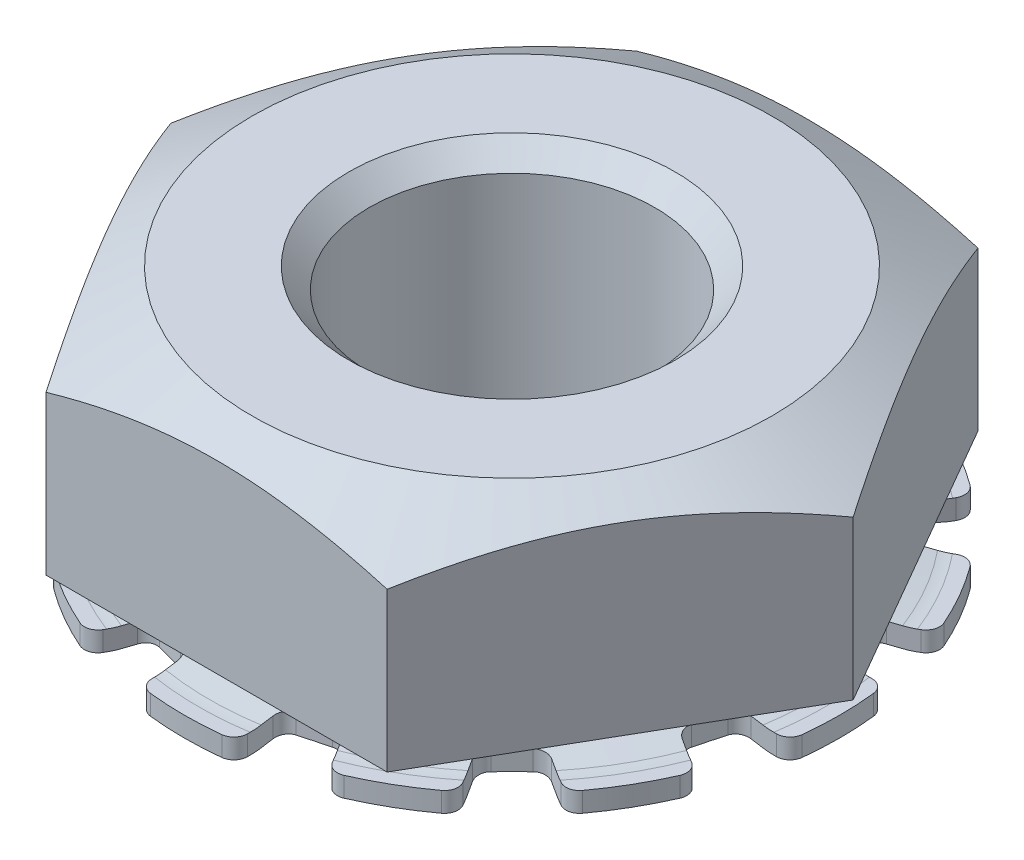
SolidWorks part; units mm, degrees
note: The reader was unsure of these and kept them because the rebuilt part matched: shared geometry of "草图1<3>".
material "铸造碳钢"
ref_plane "前视基准面" through (0, 0, 0) normal (0, 0, 1) x (1, 0, 0)
ref_plane "上视基准面" through (0, 0, 0) normal (0, 1, 0) x (1, 0, 0)
ref_plane "右视基准面" through (0, 0, 0) normal (1, 0, 0) x (0, 0, -1)
sketch "草图1" plane through (0, 0, 0) normal (0, 0, 1) x (1, 0, 0)
  line L0 (0, -97.5064) -> (0, 4777.8117) construction
  line L3 (2.085, 3.28) -> (2.085, 0)
  line L4 (2.085, 0) -> (2.685, 0)
  line L5 (2.685, 0) -> (2.685, 0.29)
  line L6 (2.685, 0.29) -> (2.375, 0.29)
  line L7 (2.375, 0.29) -> (2.375, 0.58)
  line L8 (2.375, 0.58) -> (4.318, 0.58)
  line L9 (4.318, 0.58) -> (4.318, 3.28)
  line L17 (2.375, 0.29) -> (2.085, 0.29) construction
  line L18 (4.5, 0) -> (4.79, 0)
  line L19 (4.5, 0.29) -> (4.79, 0.29)
  line L21 (4.79, 0.29) -> (4.79, 0)
  line L22 (2.685, 0) -> (4.5, 0) construction
  line L23 (2.685, 0.29) -> (4.5, 0)
  line L24 (2.685, 0.58) -> (4.5, 0.29)
  line L25 (2.385, 3.58) -> (3.7984, 3.58)
  line L26 (3.7984, 3.58) -> (4.318, 3.28)
  line L27 (2.385, 3.58) -> (2.085, 3.28)
  dimension "D1" = 45
  dimension "螺纹大径" = 4.17
  dimension "外齿直径" = 9.58
  dimension "螺母厚度" = 3
  dimension "螺母总厚度" = 3.58
  dimension "D4" = 30
  dimension "倒角" = 0.3
  dimension "底部直径" = 5.37
  dimension "六角对边" = 8.636
revolve "旋转1" add sketch "草图1" angle 360 about L0
revolve "旋转2" add sketch "草图1<3>" angle 360 about L0
sketch "草图1<3>" plane through (0, 0, 0) normal (0, 0, 1) x (1, 0, 0) same geometry as "草图1"
sketch "草图2" plane through (0, 0.58, 0) normal (0, 1, 0) x (1, 0, 0)
  line L1 (4.986, 0) -> (2.493, 4.318)
  line L2 (2.493, 4.318) -> (-2.493, 4.318)
  line L3 (-2.493, 4.318) -> (-4.986, 0)
  line L4 (-4.986, 0) -> (-2.493, -4.318)
  line L5 (-2.493, -4.318) -> (2.493, -4.318)
  line L6 (2.493, -4.318) -> (4.986, 0)
  circle A0 centre (0, 0) radius 4.318
  circle A4 centre (0, 0) radius 4.318 construction
  circle M11 centre (0, 0) radius 4.318
extrude "凸台-拉伸2" add sketch "草图2" along normal up to surface (2.7 mm away) contours L4 L3 M11 | L5 L4 M11 | L6 L5 M11 | L6 L1 M11 | L2 L1 M11 | L3 L2 M11 up to face at (4.318, 3.28, 0)
fillet "圆角1" radius 1 2 edges at (4.5, 0, 0) (4.5, 0.29, 0)
sketch "草图3" plane through (0, 0, 0) normal (0, 1, 0) x (1, 0, 0)
  line L3 (-0.6985, 4.7388) -> (-0.6985, 4.0402)
  line L4 (-0.6985, 4.0402) -> (0.6985, 4.0402) construction
  line L5 (0.6985, 4.0402) -> (0.6985, 4.7388)
  line L6 (0, 0) -> (0, 4.0402) construction
  line L7 (1.0569, 3.9442) -> (1.2397, 4.6268)
  line L8 (-1.0569, 3.9442) -> (-1.2397, 4.6268)
  line L9 (-0.6985, 4.0402) -> (-1.0569, 3.9442)
  line L10 (0.6985, 4.0402) -> (1.0569, 3.9442)
  line L11 (1.0569, 3.9442) -> (0, 0) construction
  line L12 (0, 0) -> (-1.0569, 3.9442) construction
  arc A2 (-0.6985, 4.7388) -> (-1.2397, 4.6268) centre (0, 0) ccw
  circle A3 centre (0, 0) radius 4.79 construction
  arc A4 (1.2397, 4.6268) -> (0.6985, 4.7388) centre (0, 0) ccw
  dimension "D2" = 30
  dimension "齿宽" = 1.3971
  dimension "齿高" = 0.6985
extrude "切除-拉伸1" cut sketch "草图3" along normal up to next
pattern_circular "阵列(圆周)1" count 12 over 360 about axis through (0, 0, 0) along (0, 1, 0) of "切除-拉伸1"
fillet "圆角2" radius 0.2 96 edges at (-1.0571, 0.0666, -3.9442) (-0.6985, 0.2089, -4.0402) (-1.0571, 0.3566, -3.9442) (-0.6985, 0.145, -4.7388) (1.0571, 0.0666, -3.9442) (1.0571, 0.3566, -3.9442) (0.6985, 0.2089, -4.0402) (0.6985, 0.145, -4.7388) (2.8876, 0.0666, 2.8872) (2.6251, 0.2089, 3.1497) (2.8876, 0.3566, 2.8872) (3.1497, 0.2089, 2.6251) (2.9744, 0.145, 3.7546) (3.7546, 0.145, 2.9744) (1.0571, 0.0666, 3.9442) (0.6985, 0.2089, 4.0402) (1.0571, 0.3566, 3.9442) (1.4152, 0.2089, 3.8482) (0.6985, 0.145, 4.7388) (1.7644, 0.145, 4.4532) (3.9442, 0.0666, -1.0571) (4.0402, 0.2089, -0.6985) (3.9442, 0.3566, -1.0571) (3.8482, 0.2089, -1.4152) (4.7388, 0.145, -0.6985) (4.4532, 0.145, -1.7644) (3.9443, 0.0666, 1.0567) (3.8482, 0.2089, 1.4152) (3.9443, 0.3566, 1.0567) (4.0402, 0.2089, 0.6985) (4.4532, 0.145, 1.7644) (4.7388, 0.145, 0.6985) (-3.9442, 0.0666, 1.0571) (-4.0402, 0.2089, 0.6985) (-3.9442, 0.3566, 1.0571) (-3.8482, 0.2089, 1.4152) (-4.7388, 0.145, 0.6985) (-4.4532, 0.145, 1.7644) (-3.9443, 0.0666, -1.0567) (-3.8482, 0.2089, -1.4152) (-3.9443, 0.3566, -1.0567) (-4.0402, 0.2089, -0.6985) (-4.4532, 0.145, -1.7644) (-4.7388, 0.145, -0.6985) (-1.4152, 0.2089, -3.8482) (-1.7644, 0.145, -4.4532) (-1.0567, 0.0666, 3.9443) (-1.4152, 0.2089, 3.8482) (-1.0567, 0.3566, 3.9443) (-0.6985, 0.2089, 4.0402) (-1.7644, 0.145, 4.4532) (-0.6985, 0.145, 4.7388) (-2.8872, 0.0666, 2.8876) (-3.1497, 0.2089, 2.6251) (-2.8872, 0.3566, 2.8876) (-2.6251, 0.2089, 3.1497) (-3.7546, 0.145, 2.9744) (-2.9744, 0.145, 3.7546) (2.8872, 0.0666, -2.8876) (3.1497, 0.2089, -2.6251) (2.8872, 0.3566, -2.8876) (2.6251, 0.2089, -3.1497) (3.7546, 0.145, -2.9744) (2.9744, 0.145, -3.7546) (1.4152, 0.2089, -3.8482) (1.7644, 0.145, -4.4532) (-2.8876, 0.0666, -2.8872) (-2.6251, 0.2089, -3.1497) (-2.8876, 0.3566, -2.8872) (-3.1497, 0.2089, -2.6251) (-2.9744, 0.145, -3.7546) (-3.7546, 0.145, -2.9744)
